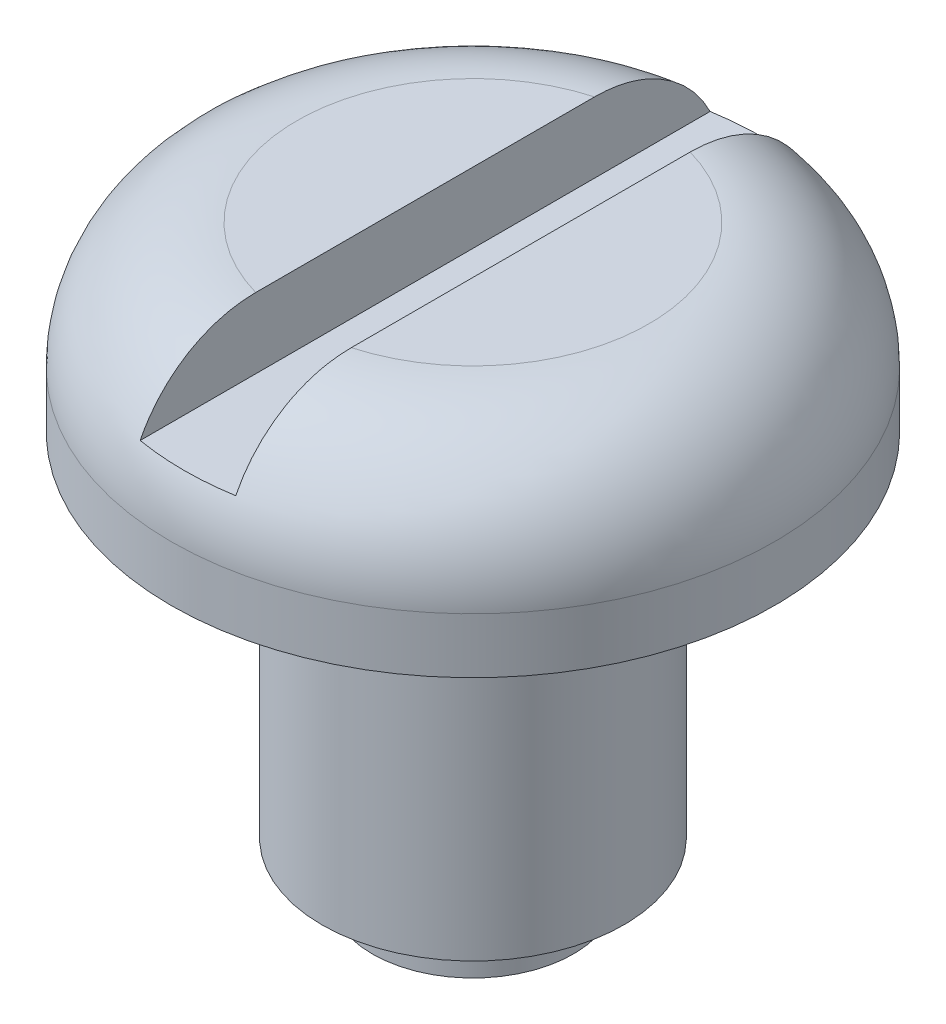
SolidWorks part; units mm, degrees
ref_plane "Front Plane" through (0, 0, 0) normal (0, 0, 1) x (1, 0, 0)
ref_plane "Top Plane" through (0, 0, 0) normal (0, 1, 0) x (1, 0, 0)
ref_plane "Right Plane" through (0, 0, 0) normal (1, 0, 0) x (0, 0, -1)
sketch "Sketch1" plane through (0, 0, 0) normal (0, 1, 0) x (1, 0, 0)
  circle A0 centre (0, 0) radius 2
  circle A1 centre (0, 0) radius 3
  circle A2 centre (0, 0) radius 6
  dimension "D1" = 4
  dimension "D2" = 6
  dimension "D3" = 12
extrude "Boss-Extrude1" add sketch "Sketch1" against normal blind 11.6 contours A0 region at (0, 0, 0)
extrude "Boss-Extrude2" add sketch "Sketch1<3>" against normal blind 10.6 contours A1 A0 region at (-2.9151, 0, 0)
sketch "Sketch1<3>" plane through (0, 0, 0) normal (0, 1, 0) x (1, 0, 0) same geometry as "Sketch1"
extrude "Boss-Extrude3" add sketch "Sketch1<4>" against normal blind 3.6 contours A2 A1 region at (-5.8303, 0, 0)
sketch "Sketch1<4>" plane through (0, 0, 0) normal (0, 1, 0) x (1, 0, 0) same geometry as "Sketch1"
fillet "Fillet1" radius 2.5 1 edges at (0, 0, 6)
sketch "Sketch2" plane through (0, 0, 0) normal (0, 1, 0) x (1, 0, 0)
  line L1 (-0.95, 6.244) -> (0.95, 6.244)
  line L2 (-0.95, 6.244) -> (-0.95, -6.244)
  line L3 (-0.95, -6.244) -> (0.95, -6.244)
  line L4 (0.95, 6.244) -> (0.95, -6.244)
  line L5 (-0.95, 6.244) -> (0.95, -6.244) construction
  line L6 (-0.95, -6.244) -> (0.95, 6.244) construction
  point P0 (0, 0)
  dimension "D1" = 1.9
extrude "Cut-Extrude1" cut sketch "Sketch2" against normal blind 1.4
